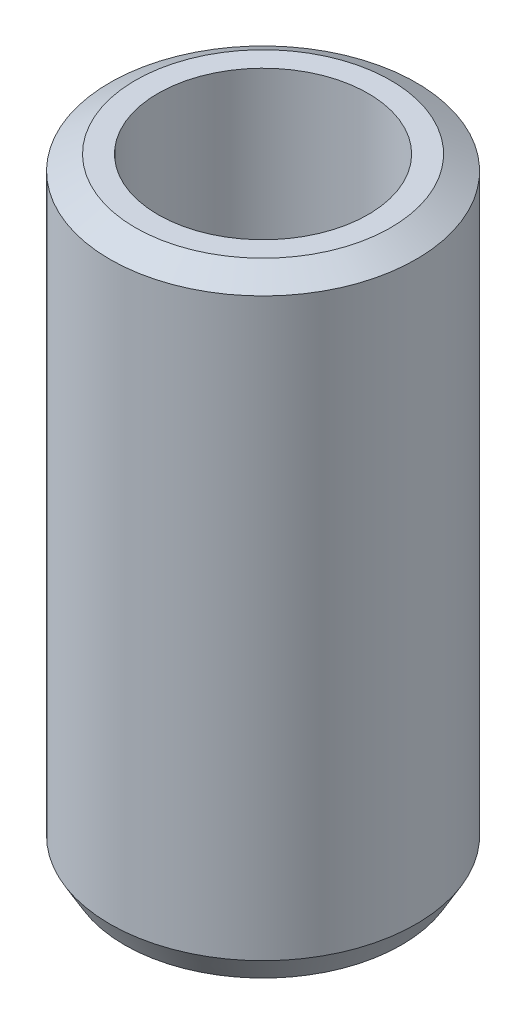
SolidWorks part; units mm, degrees
ref_plane "Front Plane" through (0, 0, 0) normal (0, 0, 1) x (1, 0, 0)
ref_plane "Top Plane" through (0, 0, 0) normal (0, 1, 0) x (1, 0, 0)
ref_plane "Right Plane" through (0, 0, 0) normal (1, 0, 0) x (0, 0, -1)
sketch "Sketch1" plane through (0, 0, 0) normal (0, 1, 0) x (1, 0, 0)
  circle A0 centre (0, 0) radius 40
  dimension "SHAFT_OD" = 80
extrude "Boss-Extrude1" add sketch "Sketch1" along normal blind 160.8727
sketch "Sketch2" plane through (0, 0, 0) normal (0, 1, 0) x (1, 0, 0)
  circle A0 centre (0, 0) radius 27.449
  dimension "BORE_D" = 54.8979
extrude "Cut-Extrude1" cut sketch "Sketch2" along normal through all
chamfer "Chamfer1" distance 3.8384 angle 60 2 edges at (0, 160.8727, 40) (0, 0, 40) first distance on face at (0, 160.8727, 40) first distance on face at (0, 0, 27.449)
